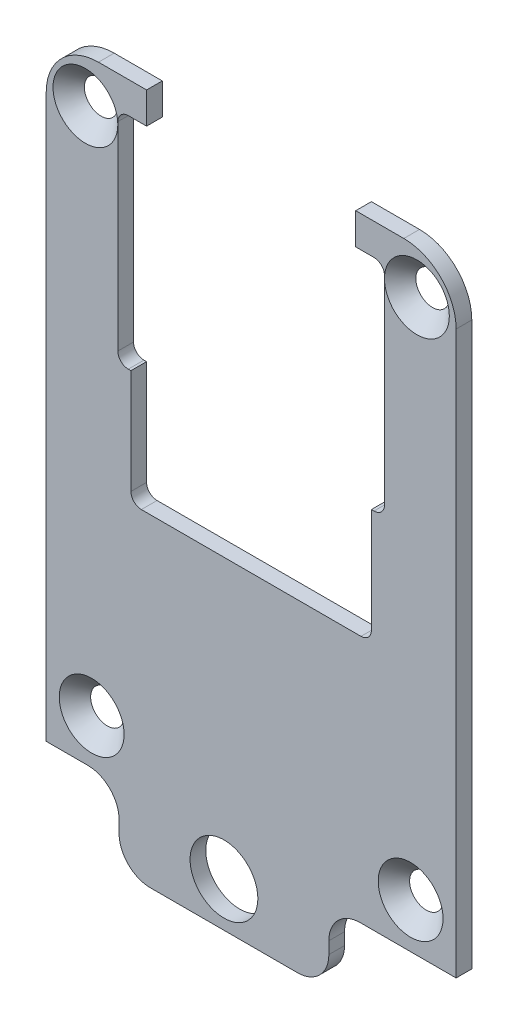
SolidWorks part; units mm, degrees
ref_plane "Front Plane" through (0, 0, 0) normal (0, 0, 1) x (1, 0, 0)
ref_plane "Top Plane" through (0, 0, 0) normal (0, 1, 0) x (1, 0, 0)
ref_plane "Right Plane" through (0, 0, 0) normal (1, 0, 0) x (0, 0, -1)
sketch "Sketch1" plane through (0, 0, 0) normal (0, 0, 1) x (1, 0, 0)
  line L0 (39.2227, 24.6544) -> (39.2227, -29.0919) construction
  line L1 (0.0227, -29.0919) -> (39.2227, -29.0919)
  line L2 (0.0227, -29.0919) -> (0.0227, 29.6544)
  line L3 (0.0227, 29.6544) -> (39.2227, 29.6544)
  line L4 (39.2227, -29.0919) -> (39.2227, 29.6544)
  line L5 (0.0227, -29.0919) -> (39.2227, 29.6544) construction
  line L6 (0.0227, 29.6544) -> (39.2227, -29.0919) construction
  line L7 (0.0227, 24.6544) -> (0.0227, -29.0919) construction
  line L8 (25.6527, -29.0919) -> (39.2227, -29.0919) construction
  line L15 (5.0227, 29.6544) -> (8.1227, 29.6544) construction
  point P4 (19.6227, 0.2812)
extrude "Base" add sketch "Sketch1" along normal blind 1.5 contours L2 L3 L4 L1
sketch "Sketch2" plane through (0, 0, 1.5) normal (0, 0, 1) x (1, 0, 0)
  line L0 (0.0227, 29.6544) -> (39.2227, 29.6544) construction
  line L1 (8.1227, 29.6544) -> (31.1227, 29.6544)
  line L2 (8.1227, 29.6544) -> (8.1227, 2.6544)
  line L3 (8.1227, 2.6544) -> (31.1227, 2.6544)
  line L4 (31.1227, 29.6544) -> (31.1227, 2.6544)
  line L5 (8.1227, 29.6544) -> (31.1227, 2.6544) construction
  line L6 (8.1227, 2.6544) -> (31.1227, 29.6544) construction
  line L7 (8.1227, 46.6159) -> (8.1227, 21.251) construction
  line L8 (6.8727, 26.6544) -> (32.3727, 26.6544)
  line L9 (6.8727, 26.6544) -> (6.8727, 5.6544)
  line L10 (6.8727, 5.6544) -> (32.3727, 5.6544)
  line L11 (32.3727, 26.6544) -> (32.3727, 5.6544)
  line L12 (6.8727, 26.6544) -> (32.3727, 5.6544) construction
  line L13 (6.8727, 5.6544) -> (32.3727, 26.6544) construction
  line L14 (8.1227, 2.6544) -> (31.1227, 2.6544)
  line L15 (8.1227, 2.6544) -> (8.1227, -5.3456)
  line L16 (8.1227, -5.3456) -> (31.1227, -5.3456)
  line L17 (31.1227, 2.6544) -> (31.1227, -5.3456)
  line L18 (8.1227, 2.6544) -> (31.1227, -5.3456) construction
  line L19 (8.1227, -5.3456) -> (31.1227, 2.6544) construction
  line L20 (31.1227, 21.251) -> (31.1227, 46.6159) construction
  line L22 (0.0227, 29.6544) -> (39.2227, 29.6544) construction
  point P4 (19.6227, 16.1544)
  point P7 (0, 0)
  point P9 (8.1602, 29.6544)
  point P11 (8.1227, 29.6544)
  point P16 (19.6227, 16.1544)
  point P17 (19.6227, -1.3456)
  point P20 (31.1227, 29.6544)
  line M8 (39.2227, 29.6544) -> (0.0227, 29.6544)
  dimension "D1" = 27
  dimension "D2" = 25.5
  dimension "D3" = 21
  dimension "D5" = 8
sketch "Sketch11" [suppressed] plane through (0, 0, 0) normal (0, 0, 1) x (1, 0, 0)
  line L0 (0.0227, -29.0919) -> (39.2227, -29.0919) construction
  line L1 (5.0927, -31.6169) -> (23.1528, -31.6169)
  line L2 (5.0927, -31.6169) -> (5.0927, -29.0919)
  line L3 (5.0927, -29.0919) -> (23.1528, -29.0919)
  line L4 (23.1528, -31.6169) -> (23.1528, -29.0919)
  line L5 (5.0927, -31.6169) -> (23.1528, -29.0919) construction
  line L6 (5.0927, -29.0919) -> (23.1528, -31.6169) construction
  arc A0 (25.6527, -29.0919) -> (23.1527, -31.5919) centre (25.6527, -31.5919) ccw construction
  point P4 (14.1228, -30.3544)
extrude "Antenna connector cover" [suppressed] add sketch "Sketch11" along normal up to surface (1.5 mm away)
fillet "Antenna connector fillet" [suppressed] radius 2.5
fillet "Front fillet" radius 5 2 edges at (0.0227, 29.6544, 0.75) (39.2227, 29.6544, 0.75)
sketch "Sketch4" plane through (0, 0, 1.5) normal (0, 0, 1) x (1, 0, 0)
  line L0 (0.0227, -9.5456) -> (39.2227, -9.5456) construction
  line L3 (19.6227, 29.6544) -> (19.6227, -34.1456) construction
  circle A1 centre (3.7727, 25.4083) radius 1.6 construction
  circle A4 centre (34.8727, -24.7956) radius 1.6
  circle A5 centre (4.3727, -24.7956) radius 1.6
  circle A6 centre (3.7727, 25.4083) radius 1.6
  circle A7 centre (35.4727, 25.4083) radius 1.6
  circle A8 centre (35.4727, 25.4083) radius 1.6 construction
extrude "Bolt hole cut" cut sketch "Sketch4" against normal up to next
chamfer "Bolt head chamber" distance 1.5 angle 45 4 edges at (37.0727, 25.4083, 1.5) (33.2727, -24.7956, 1.5) (5.9727, -24.7956, 1.5) (5.3727, 25.4083, 1.5)
extrude "Camra hole" cut sketch "Sketch2" against normal up to next contours L2 L10 L4 L8 | L9 L10 L2 L8 | L11 L8 L4 L10 | L10 L2 L3 L4 | L17 L3 L15 L16 | L2 L8 L4 M8 region at (19.6227, 28.1544, 1.5) region at (19.6227, 16.1544, 1.5) region at (7.4977, 16.1544, 1.5) region at (31.7477, 16.1544, 1.5) region at (19.6227, 4.1544, 1.5) region at (19.6227, -1.3456, 1.5)
sketch "Sketch10" plane through (0, 0, 1.5) normal (0, 0, 1) x (1, 0, 0)
  line L0 (9.8727, -15.0956) -> (29.3727, -15.0956) construction
  line L1 (9.8727, -13.3456) -> (29.3727, -13.3456)
  line L2 (9.8727, -16.8456) -> (29.3727, -16.8456)
  line L3 (8.1227, -5.3456) -> (31.1227, -5.3456) construction
  line L5 (8.1227, 5.6544) -> (8.1227, -5.3456) construction
  line L6 (31.1227, 5.6544) -> (31.1227, -5.3456) construction
  arc A0 (9.8727, -13.3456) -> (9.8727, -16.8456) centre (9.8727, -15.0956) ccw
  arc A1 (29.3727, -16.8456) -> (29.3727, -13.3456) centre (29.3727, -15.0956) ccw
  point P2 (19.6227, -15.0956)
  dimension "D1" = 3.5
  dimension "D2" = 8
extrude "GoPro strap holder" [suppressed] cut sketch "Sketch10" against normal up to next
sketch "Sketch9" plane through (0, 0, 1.5) normal (0, 0, 1) x (1, 0, 0)
  line L0 (9.6227, 21.251) -> (9.6227, 46.6159) construction
  line L1 (8.1227, 29.6544) -> (9.6227, 29.6544)
  line L2 (8.1227, 29.6544) -> (8.1227, 26.6544)
  line L3 (8.1227, 26.6544) -> (9.6227, 26.6544)
  line L4 (9.6227, 29.6544) -> (9.6227, 26.6544)
  line L5 (8.1227, 29.6544) -> (9.6227, 26.6544) construction
  line L6 (8.1227, 26.6544) -> (9.6227, 29.6544) construction
  line L7 (7.6217, -36.2417) -> (31.6237, -36.2417) construction
  line L8 (19.6227, -36.2417) -> (19.6227, 29.6544) construction
  line L9 (8.1227, 28.1583) -> (8.1227, 29.7583) construction
  line L10 (6.8727, 26.6544) -> (8.1227, 26.6544) construction
  line L11 (31.1227, 26.6544) -> (29.6227, 29.6544) construction
  line L12 (31.1227, 29.6544) -> (29.6227, 26.6544) construction
  line L13 (29.6227, 29.6544) -> (29.6227, 26.6544)
  line L14 (31.1227, 26.6544) -> (29.6227, 26.6544)
  line L15 (31.1227, 29.6544) -> (31.1227, 26.6544)
  line L16 (31.1227, 29.6544) -> (29.6227, 29.6544)
  line L17 (34.2227, 29.6544) -> (5.0227, 29.6544) construction
  line L18 (5.0227, 29.6544) -> (8.1227, 29.6544) construction
  point P4 (8.8727, 28.1544)
  point P21 (30.3727, 28.1544)
  line M10 (8.1227, 29.6544) -> (5.0227, 29.6544)
extrude "Camera side mount holder" add sketch "Sketch9" against normal up to surface (1.5 mm away) contours L4 L2 L3 M10 | L15 L13 L14 M10 region at (8.8727, 28.1544, 1.5) region at (30.3727, 28.1544, 1.5) up to face at (5.9727, -24.7956, 0)
fillet "Fillet1" radius 1 2 edges at (32.3727, 5.6544, 0.75) (6.8727, 5.6544, 0.75)
sketch "Sketch12" plane through (0, 0, 0) normal (0, 0, -1) x (-1, 0, 0)
  line L0 (-0.0227, -29.0919) -> (-39.2227, -29.0919) construction
  line L1 (-6.9927, -29.0919) -> (-27.0527, -29.0919)
  line L2 (-6.9927, -29.0919) -> (-6.9927, -36.2417)
  line L3 (-6.9927, -36.2417) -> (-27.0527, -36.2417)
  line L4 (-27.0527, -29.0919) -> (-27.0527, -36.2417)
  line L5 (-6.9927, -29.0919) -> (-27.0527, -36.2417) construction
  line L6 (-6.9927, -36.2417) -> (-27.0527, -29.0919) construction
  line L7 (-36.1375, -36.2417) -> (-24.0527, -36.2417) construction
  line L8 (-27.0527, -33.2417) -> (-27.0527, -32.0919) construction
  line L9 (-6.9927, -33.2417) -> (-6.9927, -32.0919) construction
  point P4 (-17.0227, -32.6668)
extrude "Antenna connector top base" add sketch "Sketch12" against normal up to surface (1.5 mm away) up to face at (37.9727, -24.7956, 1.5)
sketch "Sketch13" plane through (0, 0, 1.5) normal (0, 0, 1) x (1, 0, 0)
  circle A2 centre (17.0227, -31.9919) radius 3.24
  circle A3 centre (17.0227, -31.9919) radius 3.24
  dimension "D1" = 0.6
extrude "Antenna connector top cut" cut sketch "Sketch13" against normal up to next
fillet "Antenna top connector fillet" radius 3 4 edges at (6.9927, -29.0919, 0.75) (6.9927, -36.2417, 0.75) (27.0527, -36.2417, 0.75) (27.0527, -29.0919, 0.75)
fillet "Fillet2" radius 1 4 edges at (8.1227, -5.3456, 0.75) (31.1227, -5.3456, 0.75) (32.3727, 26.6544, 0.75) (6.8727, 26.6544, 0.75)
